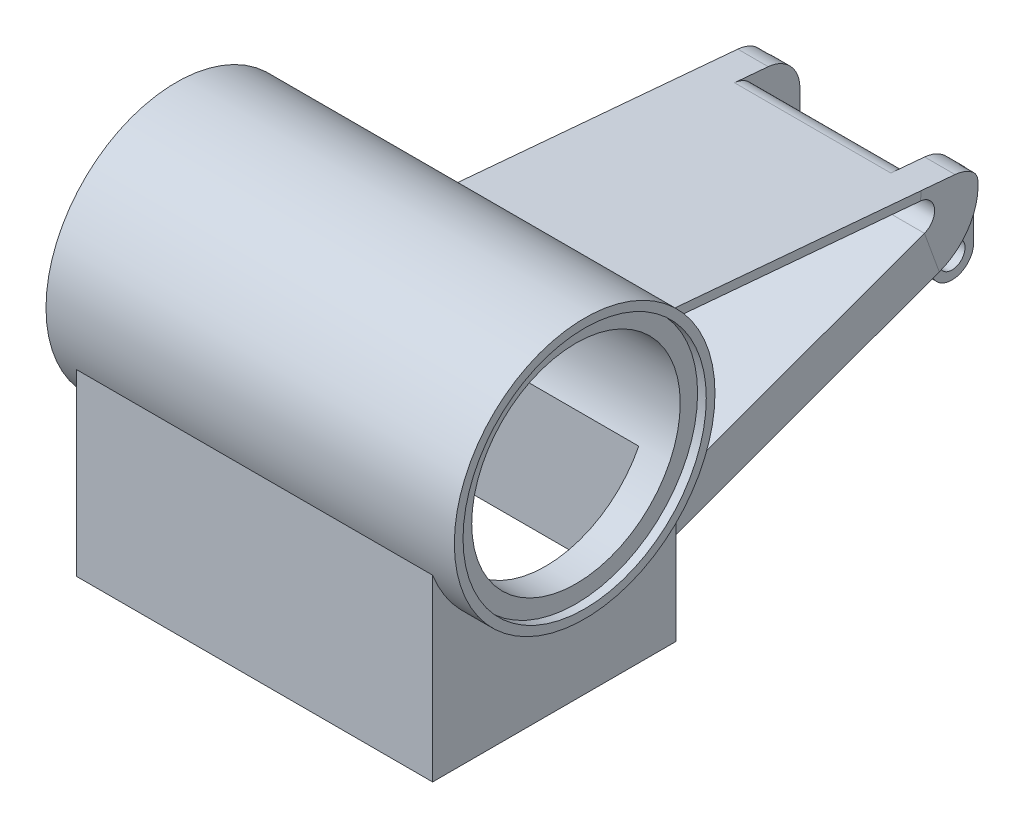
SolidWorks part; units mm, degrees
ref_plane "Front Plane" through (0, 0, 0) normal (0, 0, 1) x (1, 0, 0)
ref_plane "Top Plane" through (0, 0, 0) normal (0, 1, 0) x (1, 0, 0)
ref_plane "Right Plane" through (0, 0, 0) normal (1, 0, 0) x (0, 0, -1)
sketch "Sketch2" plane through (0, 0, 0) normal (0, 1, 0) x (1, 0, 0)
  line L0 (-47.8621, 0) -> (47.8621, 0) construction
  line L1 (0, 0) -> (0, 23.8125) construction
  line L2 (-38.1, 23.8125) -> (38.1, 23.8125)
  line L3 (-38.1, 23.8125) -> (-38.1, 22.225)
  line L4 (-38.1, 22.225) -> (38.1, 22.225)
  line L5 (38.1, 23.8125) -> (38.1, 22.225)
  line L7 (-36.5125, 22.225) -> (36.5125, 22.225)
  line L8 (-36.5125, 22.225) -> (-36.5125, 19.05)
  line L9 (-36.5125, 19.05) -> (36.5125, 19.05)
  line L10 (36.5125, 22.225) -> (36.5125, 19.05)
  line L12 (-38.1, 19.05) -> (-38.1, 17.4625)
  line L13 (-38.1, 17.4625) -> (-36.5125, 17.4625)
  line L14 (-38.1, 19.05) -> (-36.5125, 19.05)
  line L15 (-36.5125, 19.05) -> (-36.5125, 17.4625)
  point P4 (0, 0)
  dimension "D1" = 47.625
  dimension "D2" = 1.5875
  dimension "D3" = 76.2
  dimension "D4" = 1.5875
  dimension "D6" = 38.1
  dimension "D7" = 44.45
  dimension "D8" = 1.5875
  dimension "D9" = 1.5875
revolve "Revolve6" add sketch "Sketch2" angle 360 about L0 region at (-37.3063, 0, -18.2563) region at (0, 0, -23.0187) region at (0, 0, -20.6375)
ref_plane "Plane1" through (0, -41.275, 0) normal (0, 1, 0) x (1, 0, 0)
sketch "Sketch4" plane through (0, -41.275, 0) normal (0, 1, 0) x (1, 0, 0)
  line L0 (-30.9562, 20.6375) -> (30.9562, 20.6375)
  line L1 (-32.5437, -22.225) -> (32.5437, -22.225)
  line L2 (-32.5437, -22.225) -> (-32.5437, 22.225)
  line L3 (-32.5437, 22.225) -> (32.5437, 22.225)
  line L4 (32.5437, -22.225) -> (32.5437, 22.225)
  line L5 (-32.5437, -22.225) -> (32.5437, 22.225) construction
  line L6 (-32.5437, 22.225) -> (32.5437, -22.225) construction
  line L7 (30.9562, -20.6375) -> (30.9562, 20.6375)
  line L8 (-30.9562, -20.6375) -> (30.9562, -20.6375)
  line L9 (-30.9562, -20.6375) -> (-30.9562, 20.6375)
  point P0 (0, 0)
  dimension "D1" = 44.45
  dimension "D2" = 65.0875
  dimension "D3" = 1.5875
extrude "Boss-Extrude3" add sketch "Sketch4" along normal up to next separate body
extrude "Cut-Extrude9" cut sketch "Sketch4<2>" along normal up to vertex (32.7261 mm away) contours L9 L8 L7 L0 region at (0, -41.275, 0) up to point (32.5438, -8.5489, -22.225)
sketch "Sketch4<2>" plane through (0, -41.275, 0) normal (0, 1, 0) x (1, 0, 0) same geometry as "Sketch4"
sketch "Sketch5" plane through (0, 0, 0) normal (1, 0, 0) x (0, 0, -1)
  line L0 (0, 0) -> (22.225, 0) construction
  line L1 (22.225, 0) -> (79.7595, -5.0336)
  line L2 (22.225, -34.925) -> (80.884, -13.5749)
  line L3 (22.225, -8.5489) -> (22.225, -41.275) construction
  line L4 (-22.225, -41.275) -> (22.225, -41.275) construction
  line L5 (22.225, 0) -> (22.225, -34.925) construction
  arc A1 (80.884, -13.5749) -> (79.7595, -5.0336) centre (79.375, -9.4289) ccw
  circle A2 centre (0, 0) radius 22.225 construction
  dimension "D5" = 57.15
  dimension "D1" = 20
  dimension "D2" = 34.925
  dimension "D3" = 25
  dimension "D4" = 6.35
ref_plane "Plane2" through (0, -34.925, -22.225) normal (0, 0.342, -0.9397) x (-1, 0, 0)
sketch "Sketch6" plane through (0, -34.925, -22.225) normal (0, 0.342, -0.9397) x (-1, 0, 0)
  line L6 (-19.8438, 1.5875) -> (19.8438, 1.5875)
  line L8 (-19.8438, 1.5875) -> (-19.8438, 0)
  line L9 (-19.8438, 0) -> (19.8438, 0)
  line L10 (19.8438, 1.5875) -> (19.8438, 0)
  point P5 (0, 0)
  dimension "D1" = 39.6875
  dimension "D2" = 1.5875
sweep "Sweep1" add profiles "Sketch6" path "Sketch5"
sketch "Sketch12" plane through (0, 0, 0) normal (1, 0, 0) x (0, 0, -1)
  line L3 (79.7595, -5.0336) -> (85.928, -5.5733)
  line L4 (79.7595, -5.0336) -> (23.8121, -0.1389) construction
  line L6 (91.7246, -11.8991) -> (91.7246, -20.4115)
  line L7 (83.7871, -9.4289) -> (83.7871, -20.4115)
  line L8 (85.928, -5.5733) -> (92.4112, -6.1405) construction
  arc A4 (83.7871, -20.4115) -> (91.7246, -20.4115) centre (87.7558, -20.4115) ccw
  arc A7 (79.7595, -5.0336) -> (83.7871, -9.4289) centre (79.375, -9.4289) cw
  arc A8 (80.884, -13.5749) -> (79.7595, -5.0336) centre (79.375, -9.4289) ccw construction
  circle A9 centre (87.7558, -20.4115) radius 2.3813
  arc A10 (80.884, -13.5749) -> (79.7595, -5.0336) centre (79.375, -9.4289) ccw construction
  arc A11 (91.7246, -11.8991) -> (85.928, -5.5733) centre (85.3746, -11.8991) ccw
  point P19 (92.4112, -6.1405)
  dimension "D1" = 7.9375
  dimension "D3" = 4.7625
  dimension "D5" = 6.35
  dimension "D2" = 14.2875
  dimension "D4" = 12.7
extrude "Boss-Extrude4" add sketch "Sketch12" along normal blind 3.175 from offset 14.2875 separate body
mirror "Mirror12" about plane through (0, 0, 0) normal (1, 0, 0) of "Boss-Extrude4"
sketch "Sketch15" plane through (19.8438, 0, 0) normal (1, 0, 0) x (0, 0, -1)
  line L7 (83.0558, -19.5419) -> (22.225, -41.6825)
  line L8 (24.3968, -40.892) -> (83.0558, -19.5419)
  line L10 (22.225, -8.5489) -> (22.225, -41.275) construction
  line L11 (79.7595, -5.0336) -> (98.3019, -6.6559) construction
  line L12 (22.225, 0) -> (79.7595, -5.0336) construction
  arc A0 (91.7246, -11.8991) -> (85.928, -5.5733) centre (85.3746, -11.8991) ccw construction
  arc A5 (83.0558, -19.5419) -> (80.313, 1.2922) centre (79.375, -9.4289) ccw
  arc A6 (83.0558, -19.5419) -> (89.9649, -7.5115) centre (79.375, -9.4289) ccw
  dimension "D1" = 6.35
ref_plane "Plane4" through (19.8438, -41.6825, -22.225) normal (0, 0.342, -0.9397) x (-1, 0, 0)
sketch "Sketch14" plane through (17.5325, -35.7155, -20.0532) normal (0, 0.342, -0.9397) x (-1, 0, 0)
  line L1 (0.07, 0) -> (-2.3112, 0)
  line L2 (0.07, 0) -> (0.07, -6.35)
  line L3 (0.07, -6.35) -> (-2.3112, -6.35)
  line L4 (-2.3112, 0) -> (-2.3112, -6.35)
  line L5 (0.07, -10.132) -> (0.07, -2.133) construction
  dimension "D1" = 6.35
sweep "Sweep5" add profiles "Sketch14" path "Sketch15"
sketch "Sketch20" plane through (0, 0, 0) normal (1, 0, 0) x (0, 0, -1)
  line L0 (83.7165, -8.6428) -> (89.9649, -7.5115)
  line L1 (79.7595, -5.0336) -> (85.928, -5.5733)
  line L2 (85.928, -5.5733) -> (79.7595, -5.0336) construction
  arc A0 (85.928, -5.5733) -> (89.9649, -7.5115) centre (85.3746, -11.8991) cw
  arc A1 (79.7595, -5.0336) -> (83.7165, -8.6428) centre (79.375, -9.4289) cw
  arc A2 (89.9649, -7.5115) -> (85.928, -5.5733) centre (85.3746, -11.8991) ccw construction
extrude "Boss-Extrude8" add sketch "Sketch20" along normal up to surface (3.9688 mm away) from offset 15.875
mirror "Mirror9" about plane through (0, 0, 0) normal (1, 0, 0) of "Boss-Extrude8", "Sweep5"
sketch "Sketch18" plane through (0, 0, -22.225) normal (0, 0, -1) x (-1, 0, 0)
  line L0 (-32.5437, -41.275) -> (-19.8438, -41.275) construction
  line L1 (-17.4625, -34.925) -> (17.4625, -34.925)
  line L2 (-17.4625, -34.925) -> (-17.4625, -41.275)
  line L3 (-17.4625, -41.275) -> (17.4625, -41.275)
  line L4 (17.4625, -34.925) -> (17.4625, -41.275)
  line L5 (17.4625, -41.6825) -> (17.4625, -19.5419) construction
extrude "Cut-Extrude10" cut sketch "Sketch18" against normal up to next
fillet "Fillet4" radius 2.54 6 edges at (18.6531, -35.7155, -20.0532) (-18.6531, -35.7155, -20.0532) (18.6531, -41.6825, -22.225) (-18.6531, -41.6825, -22.225) (-18.6531, -7.5115, -89.9649) (18.6531, -7.5115, -89.9649)
fillet "Fillet5" radius 5.08 2 edges at (17.4625, -14.3369, -83.7871) (-17.4625, -14.3369, -83.7871)
sketch "Sketch21" plane through (-38.1, 0, 0) normal (-1, 0, 0) x (0, 0, 1)
  circle A14 centre (0, 0) radius 22.225
  circle A15 centre (0, 0) radius 22.225
  circle A17 centre (0, 0) radius 23.8125
  circle A18 centre (0, 0) radius 23.8125
  dimension "D1" = 0
  dimension "D2" = 0
extrude "Cut-Extrude11" cut sketch "Sketch21" against normal up to surface (1.5875 mm away) up to face at (-36.5125, 0, 19.05)
